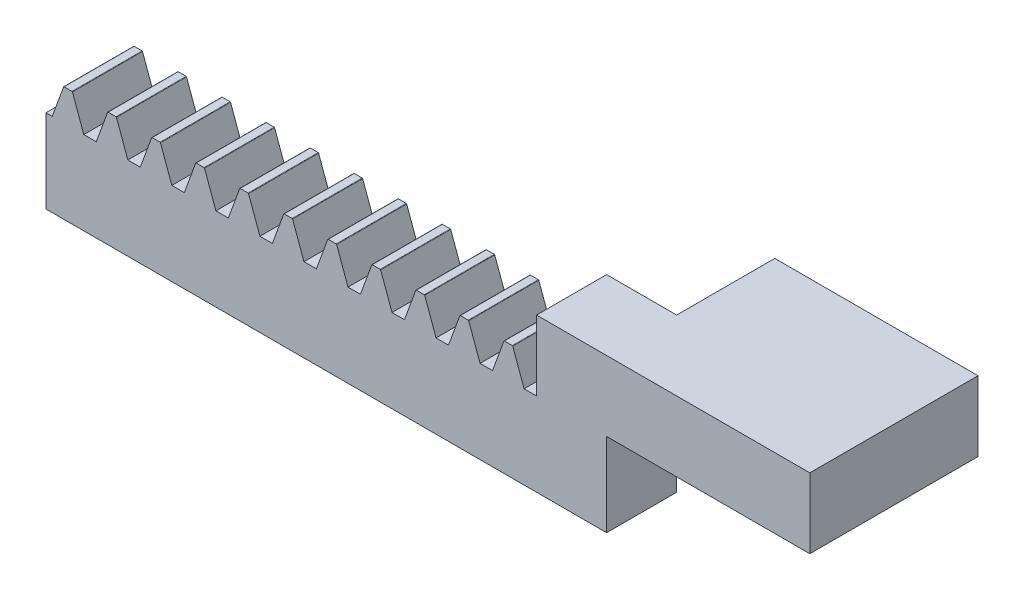
SolidWorks part; units mm, degrees
extrude "Blank" add sketch "BlankSke" against normal blind 5
sketch "BlankSke" plane through (0, 0, 0) normal (0, 0, 1) x (1, 0, 0)
  line L1 (0, 0) -> (40, 0)
  line L2 (0, 0) -> (0, 8.2)
  line L3 (0, 8.2) -> (40, 8.2)
  line L4 (40, 0) -> (40, 8.2)
  dimension "Length" = 40
ref_plane "Plane1" through (0, 0, 0) normal (0, 0, 1) x (1, 0, 0)
ref_plane "Plane2" through (0, 0, 0) normal (0, 1, 0) x (1, 0, 0)
ref_plane "Plane3" through (0, 0, 0) normal (1, 0, 0) x (0, 0, -1)
sketch "HoldingSke" plane through (0, 0, 0) normal (0, 1, 0) x (1, 0, 0)
  line L0 (0, 0) -> (0.1392, 0.9903)
  line L1 (-15, 0) -> (100, 0) construction
  line L2 (0, 0) -> (-2.1039, 2.3779)
  line L3 (0, 0) -> (-11.863, 4.5341)
  line L4 (0, 0) -> (8.3795, 2.0892)
  line L5 (0, 0) -> (-23.7986, -8.8762)
  line L6 (0, 0) -> (-10.5278, -7.1032)
  line L9 (-71.009, 38.7566) -> (-33.4213, 52.4374)
  line L10 (-76.2, 3.3779) -> (-69, 3.3779)
  line L11 (0, 0) -> (-5, 0)
  line L12 (-76.2, 101.6) -> (-76.162, 101.6)
  line L13 (24.9733, 27.94) -> (52.9518, 28.4284)
  line L14 (24.9733, 27.94) -> (24.9743, 27.94)
  line L15 (24.9733, 27.94) -> (100.4006, 29.5858)
  circle A0 centre (0, 0) radius 19.05
  circle A1 centre (0, 0) radius 3.6
  circle A2 centre (0, 0) radius 12.7
  dimension "Num_teeth" = 14
  dimension "Width" = 5
  dimension "Length" = 40
  dimension "Pitch_height" = 7.2
sketch "TooCutSkeIll" plane through (0, 0, 0) normal (0, 0, 1) x (1, 0, 0)
  line L0 (-1.2538, 8.1737) -> (-0.5045, 6.1152)
  line L1 (-0.2687, 5.95) -> (0.2687, 5.95)
  line L2 (0.5045, 6.1152) -> (1.2538, 8.1737)
  line L3 (40, 8.2) -> (0, 8.2) construction
  line L4 (0, 0) -> (0, 64.897) construction
  line L5 (-13.208, 7.2) -> (12.954, 7.2) construction
  line L6 (0, 0) -> (40, 0) construction
  line L7 (0.8994, 7.2) -> (0.8994, 48.7463) construction
  line L8 (-0.8994, 7.2) -> (-0.8994, 48.7463) construction
  line L9 (1.2914, 8.2) -> (1.2914, 8.2254)
  line L10 (-1.2914, 8.2) -> (-1.2914, 8.2254)
  line L11 (-1.2914, 8.2254) -> (1.2914, 8.2254)
  arc A0 (0.2687, 5.95) -> (0.5045, 6.1152) centre (0.2687, 6.201) ccw
  arc A1 (-0.5045, 6.1152) -> (-0.2687, 5.95) centre (-0.2687, 6.201) ccw
  arc A2 (1.2914, 8.2) -> (1.2538, 8.1737) centre (1.2914, 8.16) ccw
  arc A3 (-1.2538, 8.1737) -> (-1.2914, 8.2) centre (-1.2914, 8.16) ccw
  dimension "Addendum_plus" = 1.0254
  dimension "Pitch_height" = 7.2
  dimension "Pressure_angle" = 20
  dimension "Gap_width" = 1.7988
  dimension "Dedendum" = 1.25
extrude "ToothCutIll" cut sketch "TooCutSkeIll" against normal through all
sketch "TooCutSkeSim" plane through (0, 0, 0) normal (0, 0, 1) x (1, 0, 0)
  line L0 (0.4444, 5.95) -> (-0.4444, 5.95)
  line L1 (1.2726, 8.2254) -> (0.4444, 5.95)
  line L2 (0, 17.4625) -> (0, 53.467) construction
  line L3 (1.2726, 8.2254) -> (-1.2726, 8.2254)
  line L6 (-1.2726, 8.2254) -> (-0.4444, 5.95)
  line L9 (-0.8994, 7.2) -> (0.8994, 7.2) construction
  line L10 (0, 0) -> (40, 0) construction
  line L11 (0.8994, 7.2) -> (0.8994, 53.467) construction
  line L12 (-0.8994, 7.2) -> (-0.8994, 53.467) construction
  dimension "Addendum_plus" = 1.0254
  dimension "Pitch_height" = 7.2
  dimension "Pressure_angle" = 20
  dimension "Gap_width" = 1.7988
  dimension "Dedendum" = 1.25
extrude "ToothCutSim" cut sketch "TooCutSkeSim" against normal through all
pattern_linear "TeethCuts" count 14 spacing 3.1416 along (1, 0, 0) of "ToothCutIll", "ToothCutSim"
sketch "Sketch1" plane through (0, 0, 0) normal (0, 0, 1) x (1, 0, 0)
  line L0 (35.002, 5.95) -> (40, 5.95)
  line L1 (40, 0) -> (40, 7.0387) construction
  line L2 (40, 5.95) -> (40, 8.2)
  line L3 (40, 8.2) -> (35.002, 8.2)
  line L4 (35.002, 8.2) -> (35.002, 5.95)
extrude "Boss-Extrude1" add sketch "Sketch1" against normal blind 5
sketch "Sketch3" plane through (0, 0, 0) normal (0, 0, 1) x (1, 0, 0)
  line L1 (35.002, 5.95) -> (40, 5.95)
  line L2 (35.002, 5.95) -> (35.002, 8.2)
  line L3 (35.002, 8.2) -> (40, 8.2)
  line L4 (40, 5.95) -> (40, 8.2)
sketch "Sketch4" plane through (40, 0, 0) normal (1, 0, 0) x (0, 0, -1)
  line L1 (0, 8.2) -> (12, 8.2)
  line L2 (0, 8.2) -> (0, 5.95)
  line L3 (0, 5.95) -> (12, 5.95)
  line L4 (12, 8.2) -> (12, 5.95)
  line L7 (0, 0) -> (0, 8.2) construction
  line L8 (5, 8.2) -> (0, 8.2) construction
  line L9 (0, 0) -> (0, 8.2) construction
  dimension "D1" = 12
  dimension "D2" = 2.25
extrude "Boss-Extrude4" add sketch "Sketch4" along normal blind 14.5
sketch "Sketch6" plane through (0, 8.2, 0) normal (0, 1, 0) x (1, 0, 0)
  line L10 (35.002, 5) -> (35.002, 0)
  line L24 (35.002, 5) -> (35.002, 0)
  line L34 (40, 5) -> (35.002, 5)
  line L35 (40, 5) -> (35.002, 5)
  line L57 (35.002, 0) -> (54.5, 0)
  line L59 (35.002, 0) -> (54.5, 0)
  line L61 (54.5, 0) -> (54.5, 12)
  line L62 (54.5, 0) -> (54.5, 12)
  line L63 (54.5, 12) -> (40, 12)
  line L64 (54.5, 12) -> (40, 12)
  line L65 (40, 12) -> (40, 5)
  line L66 (40, 12) -> (40, 5)
  dimension "D1" = 0
extrude "Boss-Extrude5" add sketch "Sketch6" along normal blind 2.75
ref_plane "Plane4" through (0, 0, -2.5) normal (0, 0, -1) x (-1, 0, 0)
equation "' \"Module@HoldingSke\" = 6.35"
equation "' \"Num_teeth@HoldingSke\" = 12"
equation "' \"Ap@HoldingSke\" =  20"
equation "' \"Ap@HoldingSke\" = 20"
equation "' \"Width@HoldingSke\" = 0.25 * 25.4"
equation "' \"Show_teeth@HoldingSke\" = 500"
equation "' \"Backlash@HoldingSke\" = 0.009 * 25.4"
equation "' \"Addendum_fac@HoldingSke\" = 1.0"
equation "' \"Dedendum_fac@HoldingSke\" = 1.25"
equation "' \"Dedendum_add@HoldingSke\" = 0.00005 * 25.4"
equation "' \"Clearance_fac@HoldingSke\" = 0.25"
equation "' \"Pitch_height@HoldingSke\" = 1 * 25.4"
equation "' \"Length@HoldingSke\" = 4.71 * 25.4"
equation "\"Pitch@HoldingSke\" = 1 / \"Module@HoldingSke\""
equation "\"MPH@HoldingSke\" = \"Dedendum_fac@HoldingSke\" / \"Pitch@HoldingSke\" + 2 * \"Dedendum_add@HoldingSke\" + 0.002 * 25.4"
equation "\"MPH@HoldingSke\" = ((sgn( \"MPH@HoldingSke\" - \"Pitch_height@HoldingSke\")+1)*( \"MPH@HoldingSke\" - \"Pitch_height@HoldingSke\"))/2 + \"Pitch_height@HoldingSke\""
equation "\"Blank_height@BlankSke\" = \"Pitch_height@HoldingSke\" + \"Addendum_fac@HoldingSke\"  / \"Pitch@HoldingSke\" "
equation "\"Length@BlankSke\" =  \"Length@HoldingSke\""
equation "\"Face_width@Blank\" = \"Width@HoldingSke\""
equation "\"Pressure_angle@TooCutSkeIll\" = \"Ap@HoldingSke\""
equation "\"Addendum_plus@TooCutSkeIll\" =  \"Addendum_fac@HoldingSke\"  / \"Pitch@HoldingSke\" + 0.001 *25.4"
equation "\"Dedendum@TooCutSkeIll\" = \"Dedendum_fac@HoldingSke\"  / \"Pitch@HoldingSke\""
equation "\"Pitch_height@TooCutSkeIll\" =  \"MPH@HoldingSke\""
equation "\"Gap_width@TooCutSkeIll\" = 3.14159265 / 2 / \"Pitch@HoldingSke\" + 6 * \"Backlash@HoldingSke\""
equation "\"Pressure_angle@TooCutSkeSim\" = \"Ap@HoldingSke\""
equation "\"Addendum_plus@TooCutSkeSim\" =  \"Addendum_fac@HoldingSke\"  / \"Pitch@HoldingSke\" + 0.001 * 25.4"
equation "\"Dedendum@TooCutSkeSim\" = \"Dedendum_fac@HoldingSke\"  / \"Pitch@HoldingSke\""
equation "\"Pitch_height@TooCutSkeSim\" =  \"MPH@HoldingSke\""
equation "\"Gap_width@TooCutSkeSim\" = 3.14159265 / 2 / \"Pitch@HoldingSke\" + 6 * \"Backlash@HoldingSke\""
equation "\"Root_fillet@TooCutSkeIll\" = \"Clearance_fac@HoldingSke\" / \"Pitch@HoldingSke\" + \"Dedendum_add@HoldingSke\""
equation "\"Break_rad@TooCutSkeIll\" = 0.02 / \"Pitch@HoldingSke\" * 2"
equation "\"Linear_pitch@TeethCuts\" = 3.14159265 / \"Pitch@HoldingSke\""
equation "\"Num_teeth@HoldingSke\" = int( ( \"Length@HoldingSke\" + 0 ) / (3.14159265 / \"Pitch@HoldingSke\")) + 0.9999  + 1"
equation " \"Num_teeth@TeethCuts\" = int( \"Show_teeth@HoldingSke\" ) + 1"
equation " \"Num_teeth@TeethCuts\" = ((sgn( \"Num_teeth@TeethCuts\" - \"Num_teeth@HoldingSke\" )-1)*( \"Num_teeth@TeethCuts\" - \"Num_teeth@HoldingSke\" ))/-2+ \"Num_teeth@HoldingSke\""
equation " \"Num_teeth@TeethCuts\" = ((sgn( \"Num_teeth@TeethCuts\" - 2.0)+1)*( \"Num_teeth@TeethCuts\" - 2.0))/2 +2.0"
